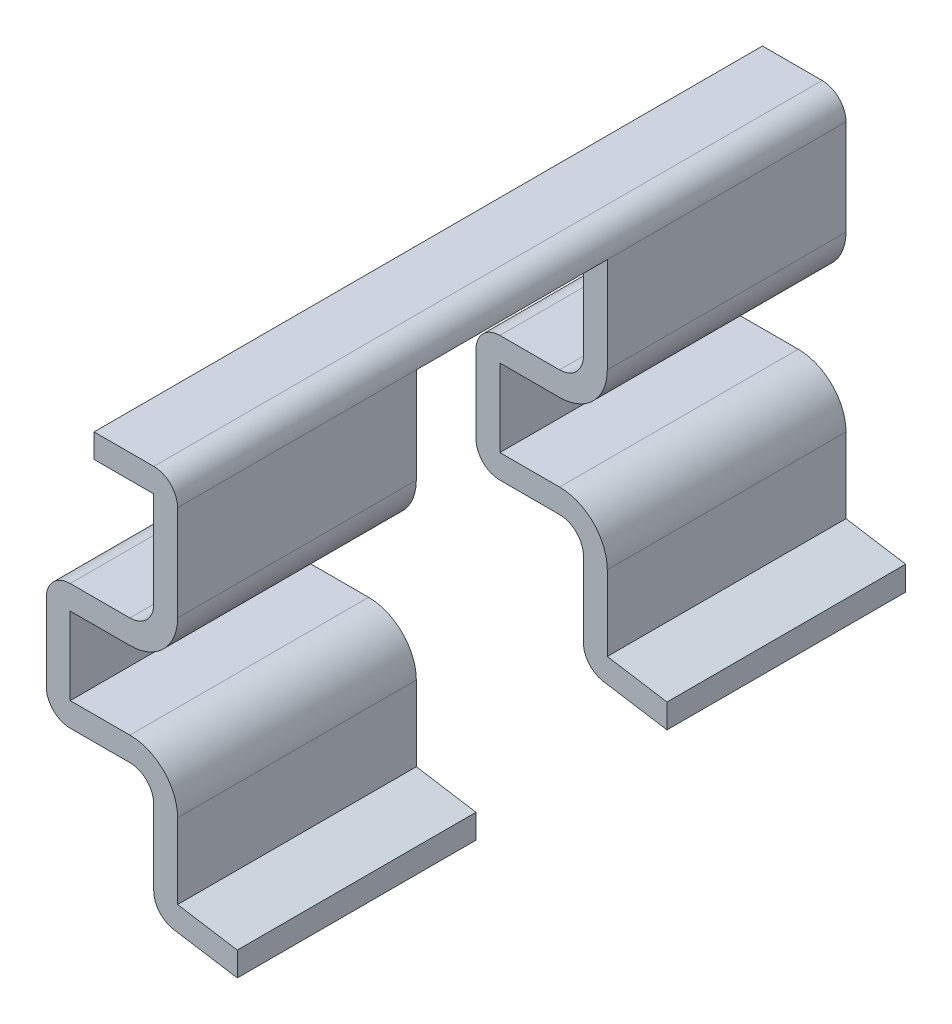
SolidWorks part; units mm, degrees
ref_plane "Front Plane" through (0, 0, 0) normal (0, 0, 1) x (1, 0, 0)
ref_plane "Top Plane" through (0, 0, 0) normal (0, 1, 0) x (1, 0, 0)
ref_plane "Right Plane" through (0, 0, 0) normal (1, 0, 0) x (0, 0, -1)
sketch "Sketch1" plane through (0, 0, 0) normal (0, 0, 1) x (1, 0, 0)
  line L0 (0, 39.6686) -> (0, -39.6686) construction
  line L1 (-50.3702, -14.1004) -> (-50.3702, -7.1004) construction
  line L2 (0, 31.3996) -> (0, -17.1004)
  line L3 (-61.0241, 31.3996) -> (61.0241, 31.3996) construction
  line L4 (-50.3702, -9.1004) -> (-50.3702, -17.1004)
  line L5 (-52.3702, -7.1004) -> (-57.3702, -7.1004)
  line L6 (-52.3702, 3.3996) -> (-57.3702, 3.3996)
  line L7 (-59.3702, -5.1004) -> (-59.3702, 1.3996)
  line L8 (-50.3702, 5.3996) -> (-50.3702, 13.3996)
  line L9 (-50.3702, 17.1114) -> (54.6448, 17.1114) construction
  line L10 (-22.5495, 17.6114) -> (22.5495, 17.6114)
  line L12 (48.6873, 13.6699) -> (25.7209, 17.3583)
  line L13 (50.3702, 5.3996) -> (50.3702, 11.6952)
  line L14 (59.3702, -5.1004) -> (59.3702, 1.3996)
  line L15 (52.3702, 3.3996) -> (57.3702, 3.3996)
  line L16 (52.3702, -7.1004) -> (57.3702, -7.1004)
  line L17 (50.3702, -9.1004) -> (50.3702, -17.1004)
  line L18 (-50.3702, 3.3996) -> (-50.3702, 34.3996) construction
  line L19 (-59.3702, -1.8504) -> (59.3702, -1.8504) construction
  line L20 (50.3702, -17.1004) -> (25.7209, -21.0591)
  line L37 (-50.3702, -17.1004) -> (-43.3702, -18.2246)
  line L38 (-22.5495, -21.3122) -> (22.5495, -21.3122)
  line L39 (-48.3702, -9.1004) -> (-48.3702, -15.396)
  line L40 (-48.3702, -15.396) -> (-43.3702, -16.199)
  line L41 (-22.5495, -19.3122) -> (22.5495, -19.3122)
  line L42 (48.3702, -15.396) -> (25.4037, -19.0844)
  line L43 (48.3702, -9.1004) -> (48.3702, -15.396)
  line L44 (52.3702, -5.1004) -> (57.3702, -5.1004)
  line L45 (57.3702, -5.1004) -> (57.3702, 1.3996)
  line L46 (52.3702, 1.3996) -> (57.3702, 1.3996)
  line L47 (48.3702, 5.3996) -> (48.3702, 11.6952)
  line L48 (48.3702, 11.6952) -> (25.4037, 15.3836)
  line L49 (-22.5495, 15.6114) -> (22.5495, 15.6114)
  line L51 (-48.3702, 5.3996) -> (-48.3702, 13.3996)
  line L52 (-52.3702, 1.3996) -> (-57.3702, 1.3996)
  line L53 (-57.3702, -5.1004) -> (-57.3702, 1.3996)
  line L54 (-52.3702, -5.1004) -> (-57.3702, -5.1004)
  line L55 (-28.2818, 7.1496) -> (28.2818, 7.1496) construction
  line L56 (0, 0) -> (-5.8172, 0) construction
  line L57 (-3.0332, 0) -> (3.0332, 0) construction
  line L58 (-50.3702, 13.3996) -> (-55.3702, 13.3996)
  line L59 (-50.3702, 15.3996) -> (-55.3702, 15.3996)
  line L60 (-27.2586, 17.1114) -> (-25.7209, 17.3583)
  line L61 (-43.3702, -16.199) -> (-43.3702, -18.2246)
  line L62 (-31.9404, -20.0602) -> (-25.7209, -21.0591)
  line L63 (-32.3579, -17.9676) -> (-25.4037, -19.0844)
  line L64 (-55.3702, 15.3996) -> (-55.3702, 13.3996)
  circle A1 centre (0, -12.6004) radius 32.8 construction
  arc A2 (25.7209, 17.3583) -> (22.5495, 17.6114) centre (22.5495, -2.3886) ccw
  arc A3 (-25.7209, 17.3583) -> (-22.5495, 17.6114) centre (-22.5495, -2.3886) cw
  arc A4 (59.3702, 1.3996) -> (57.3702, 3.3996) centre (57.3702, 1.3996) ccw
  arc A5 (59.3702, -5.1004) -> (57.3702, -7.1004) centre (57.3702, -5.1004) cw
  arc A6 (50.3702, -9.1004) -> (52.3702, -7.1004) centre (52.3702, -9.1004) cw
  arc A7 (50.3702, 5.3996) -> (52.3702, 3.3996) centre (52.3702, 5.3996) ccw
  arc A8 (48.6873, 13.6699) -> (50.3702, 11.6952) centre (48.3702, 11.6952) cw
  arc A10 (-52.3702, -7.1004) -> (-50.3702, -9.1004) centre (-52.3702, -9.1004) cw
  arc A11 (-50.3702, 5.3996) -> (-52.3702, 3.3996) centre (-52.3702, 5.3996) cw
  arc A12 (-57.3702, 3.3996) -> (-59.3702, 1.3996) centre (-57.3702, 1.3996) ccw
  arc A13 (-57.3702, -7.1004) -> (-59.3702, -5.1004) centre (-57.3702, -5.1004) cw
  arc A14 (25.7209, -21.0591) -> (22.5495, -21.3122) centre (22.5495, -1.3122) cw
  arc A15 (-25.7209, -21.0591) -> (-22.5495, -21.3122) centre (-22.5495, -1.3122) ccw
  arc A24 (-25.4037, -19.0844) -> (-22.5495, -19.3122) centre (-22.5495, -1.3122) ccw
  arc A25 (25.4037, -19.0844) -> (22.5495, -19.3122) centre (22.5495, -1.3122) cw
  arc A26 (48.3702, -9.1004) -> (52.3702, -5.1004) centre (52.3702, -9.1004) cw
  arc A27 (48.3702, 5.3996) -> (52.3702, 1.3996) centre (52.3702, 5.3996) ccw
  arc A28 (25.4037, 15.3836) -> (22.5495, 15.6114) centre (22.5495, -2.3886) ccw
  arc A29 (-25.4037, 15.3836) -> (-22.5495, 15.6114) centre (-22.5495, -2.3886) cw
  arc A30 (-48.3702, 5.3996) -> (-52.3702, 1.3996) centre (-52.3702, 5.3996) cw
  arc A31 (-52.3702, -5.1004) -> (-48.3702, -9.1004) centre (-52.3702, -9.1004) cw
  arc A32 (-50.3702, 15.3996) -> (-48.3702, 13.3996) centre (-50.3702, 13.3996) cw
  point P17 (0, 17.6114)
  point P71 (57.3702, -1.8504)
  point P73 (0, -19.3122)
  point P89 (0, 15.6114)
  point P97 (-57.3702, -1.8504)
  point P99 (-8.715, 7.1496)
  point P104 (0, 0)
  dimension "D1" = 65.6
  dimension "D2" = 20
  dimension "D6" = 2
  dimension "D3" = 8
  dimension "D4" = 6.5
  dimension "D5" = 5
  dimension "D7" = 5
  dimension "D8" = 8
sketch "Sketch2" plane through (0, 0, 0) normal (0, 0, 1) x (1, 0, 0)
  line L10 (-50.3702, 15.3996) -> (-55.3702, 15.3996) construction
  line L14 (-55.3702, 15.3996) -> (-55.3702, 13.3996) construction
  line L20 (-50.3702, 13.3996) -> (-55.3702, 13.3996) construction
  line L21 (-50.3702, 5.3996) -> (-50.3702, 13.3996) construction
  line L24 (-52.3702, 3.3996) -> (-57.3702, 3.3996) construction
  line L25 (-59.3702, -5.1004) -> (-59.3702, 1.3996) construction
  line L28 (-52.3702, -7.1004) -> (-57.3702, -7.1004) construction
  line L30 (-50.3702, -9.1004) -> (-50.3702, -17.1004) construction
  line L31 (-50.3702, -17.1004) -> (-43.3702, -18.2246) construction
  line L32 (-43.3702, -16.199) -> (-43.3702, -18.2246) construction
  line L35 (-48.3702, -15.396) -> (-43.3702, -16.199) construction
  line L36 (-48.3702, -9.1004) -> (-48.3702, -15.396) construction
  line L37 (-52.3702, -5.1004) -> (-57.3702, -5.1004) construction
  line L38 (-57.3702, -5.1004) -> (-57.3702, 1.3996) construction
  line L39 (-52.3702, 1.3996) -> (-57.3702, 1.3996) construction
  line L40 (-48.3702, 5.3996) -> (-48.3702, 13.3996) construction
  line L41 (-50.3702, 15.3996) -> (-55.3702, 15.3996)
  line L42 (-55.3702, 15.3996) -> (-55.3702, 13.3996)
  line L43 (-50.3702, 13.3996) -> (-55.3702, 13.3996)
  line L44 (-50.3702, 5.3996) -> (-50.3702, 13.3996)
  line L45 (-52.3702, 3.3996) -> (-57.3702, 3.3996)
  line L46 (-59.3702, -5.1004) -> (-59.3702, 1.3996)
  line L47 (-52.3702, -7.1004) -> (-57.3702, -7.1004)
  line L48 (-50.3702, -9.1004) -> (-50.3702, -17.1004)
  line L49 (-50.3702, -17.1004) -> (-43.3702, -18.2246)
  line L50 (-43.3702, -16.199) -> (-43.3702, -18.2246)
  line L51 (-48.3702, -15.396) -> (-43.3702, -16.199)
  line L52 (-48.3702, -9.1004) -> (-48.3702, -15.396)
  line L53 (-52.3702, -5.1004) -> (-57.3702, -5.1004)
  line L54 (-57.3702, -5.1004) -> (-57.3702, 1.3996)
  line L55 (-52.3702, 1.3996) -> (-57.3702, 1.3996)
  line L56 (-48.3702, 5.3996) -> (-48.3702, 13.3996)
  arc A16 (-52.3702, 3.3996) -> (-50.3702, 5.3996) centre (-52.3702, 5.3996) ccw construction
  arc A17 (-57.3702, 3.3996) -> (-59.3702, 1.3996) centre (-57.3702, 1.3996) ccw construction
  arc A18 (-59.3702, -5.1004) -> (-57.3702, -7.1004) centre (-57.3702, -5.1004) ccw construction
  arc A19 (-50.3702, -9.1004) -> (-52.3702, -7.1004) centre (-52.3702, -9.1004) ccw construction
  arc A20 (-48.3702, -9.1004) -> (-52.3702, -5.1004) centre (-52.3702, -9.1004) ccw construction
  arc A21 (-52.3702, 1.3996) -> (-48.3702, 5.3996) centre (-52.3702, 5.3996) ccw construction
  arc A22 (-48.3702, 13.3996) -> (-50.3702, 15.3996) centre (-50.3702, 13.3996) ccw construction
  arc A23 (-52.3702, 3.3996) -> (-50.3702, 5.3996) centre (-52.3702, 5.3996) ccw
  arc A24 (-57.3702, 3.3996) -> (-59.3702, 1.3996) centre (-57.3702, 1.3996) ccw
  arc A25 (-59.3702, -5.1004) -> (-57.3702, -7.1004) centre (-57.3702, -5.1004) ccw
  arc A26 (-50.3702, -9.1004) -> (-52.3702, -7.1004) centre (-52.3702, -9.1004) ccw
  arc A27 (-48.3702, -9.1004) -> (-52.3702, -5.1004) centre (-52.3702, -9.1004) ccw
  arc A28 (-52.3702, 1.3996) -> (-48.3702, 5.3996) centre (-52.3702, 5.3996) ccw
  arc A29 (-48.3702, 13.3996) -> (-50.3702, 15.3996) centre (-50.3702, 13.3996) ccw
extrude "Boss-Extrude1" add sketch "Sketch2" along normal blind 56 contours L56 A29 L41 L42 L43 L44 A23 L45 A24 L46 A25 L47 A26 L48 L49 L50 L51 L52 A27 L53 L54 L55 A28 region at (-49.2193, 14.5505, 0)
sketch "Sketch3" plane through (-59.3702, 0, 0) normal (-1, 0, 0) x (0, 0, 1)
  line L0 (56, 13.3996) -> (0, 13.3996) construction
  line L1 (56, 13.3996) -> (0, 13.3996) construction
  line L2 (28, 13.3996) -> (28, -23.2246) construction
  line L3 (56, -18.2246) -> (0, -18.2246) construction
  line L4 (20, 13.3996) -> (36, 13.3996)
  line L5 (20, 13.3996) -> (20, -23.2246)
  line L6 (20, -23.2246) -> (36, -23.2246)
  line L7 (36, 13.3996) -> (36, -23.2246)
  point P8 (28, 13.3996)
  dimension "D1" = 16
  dimension "D2" = 5
extrude "Cut-Extrude1" cut sketch "Sketch3" against normal through all
fillet "Fillet1" radius 2 2 edges at (-50.3702, -17.1004, 10) (-50.3702, -17.1004, 46)
